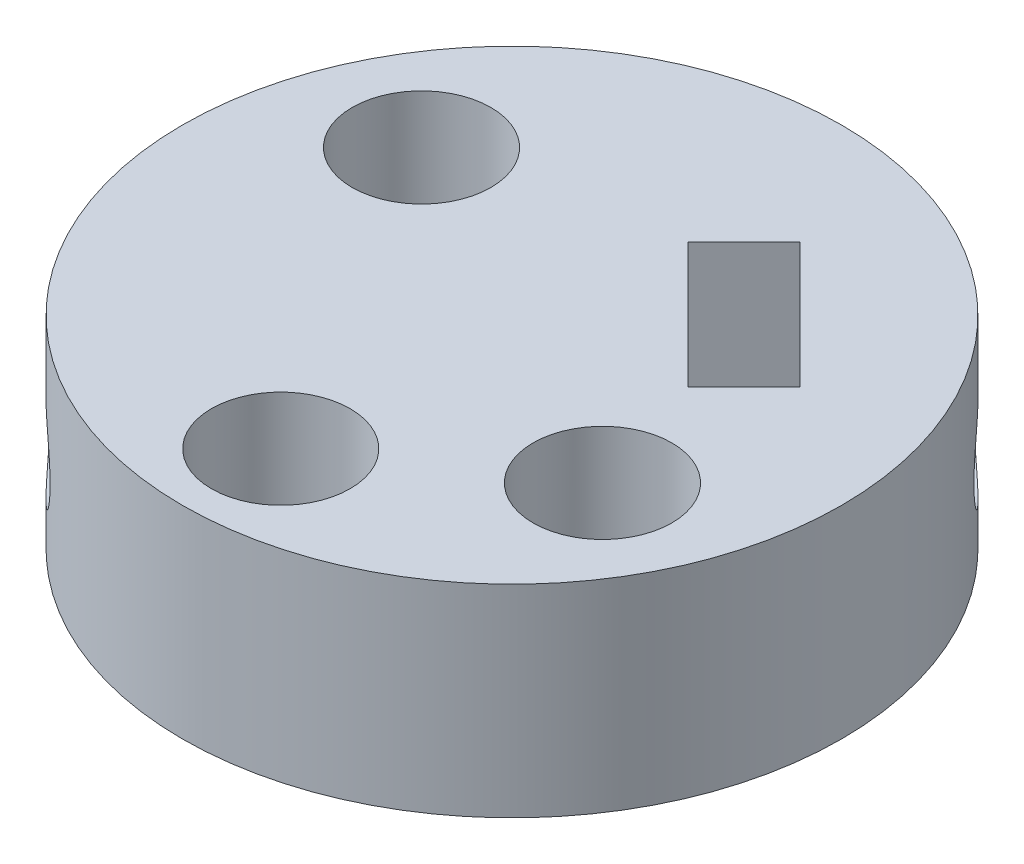
SolidWorks part; units mm, degrees
material "ABS"
ref_plane "Plano frontal" through (0, 0, 0) normal (0, 0, 1) x (1, 0, 0)
ref_plane "Plano superior" through (0, 0, 0) normal (0, 1, 0) x (1, 0, 0)
ref_plane "Plano direito" through (0, 0, 0) normal (1, 0, 0) x (0, 0, -1)
sketch "Esboço1" plane through (0, 0, 0) normal (0, 1, 0) x (1, 0, 0)
  circle A4 centre (-6.59, 3.46) radius 2.4
  circle A6 centre (6.59, -3.46) radius 2.4
  circle A8 centre (0, -8) radius 2.4
sketch "Esboço2" plane through (0, 0, 0) normal (0, 1, 0) x (1, 0, 0)
  circle A0 centre (0, 0) radius 11.4
extrude "Ressalto-extrusão3" add sketch "Esboço2" along normal blind 7
extrude "Corte-extrusão4" cut sketch "Esboço1" along normal blind 15 contours A6 | A4 | A8
sketch "Esboço3" plane through (0, 7, 0) normal (0, 1, 0) x (1, 0, 0)
  line L2 (0.8, 0.8) -> (0.8, 2.2627)
  line L3 (-0.8, 0.8) -> (-0.8, 2.2627)
  line L4 (-0.8, 2.2627) -> (-0.8, 0.8)
  line L5 (0.8, -0.8) -> (0.8, -2.2627)
  line L8 (0.8, 0.8) -> (2.2627, 0.8)
  line L9 (2.2627, 0.8) -> (0.8, 0.8)
  line L10 (0.8, -0.8) -> (2.2627, -0.8)
  line L11 (2.2627, -0.8) -> (0.8, -0.8)
  line L12 (-0.8, -0.8) -> (-2.2627, -0.8)
  line L13 (-0.8, 0.8) -> (-2.2627, 0.8)
  line L14 (-0.8, -0.8) -> (-0.8, -2.2627)
  arc A0 (0.8, 2.2627) -> (-0.8, 2.2627) centre (0, 0) ccw
  arc A1 (-2.2627, 0.8) -> (-2.2627, -0.8) centre (0, 0) ccw
  arc A2 (-0.8, -2.2627) -> (0.8, -2.2627) centre (0, 0) ccw
  arc A3 (2.2627, -0.8) -> (2.2627, 0.8) centre (0, 0) ccw
extrude "Ressalto-extrusão4" [suppressed] add sketch "Esboço3" along normal blind 9 contours L10 A3 L8 L2 A0 L3 L13 A1 L12 L14 A2 L5
sketch "Esboço4" plane through (0, 0, 0) normal (0, -1, 0) x (-1, 0, 0)
  circle A1 centre (0, 0) radius 2
sketch "Esboço6" plane through (0, 0, 0) normal (0, -1, 0) x (1, 0, 0)
  circle A0 centre (0, 0) radius 4.3
extrude "Ressalto-extrusão5" add sketch "Esboço6" along normal blind 2
extrude "Corte-extrusão7" cut sketch "Esboço4" against normal blind 5.05 and the other way blind 4
sketch "Esboço7" plane through (0, 0, 0) normal (0, -1, 0) x (1, 0, 0)
  line L0 (0, 0) -> (3.0406, -3.0406) construction
  line L1 (3.0406, -3.0406) -> (5.1972, -0.8839)
  line L2 (3.0406, -3.0406) -> (0.8485, -5.2326)
  line L3 (0.8485, -5.2326) -> (2.7931, -7.1771)
  line L4 (5.1972, -0.8839) -> (7.1418, -2.8284)
  line L5 (7.1418, -2.8284) -> (2.7931, -7.1771)
extrude "Corte-extrusão8" cut sketch "Esboço7" against normal blind 10.5 contours L5 L4 L1 L2 L3 region at (3.9952, 0, -4.0305)
sketch "Esboço8" plane through (3.0406, 0, -3.0406) normal (0.7071, 0, -0.7071) x (-0.7071, 0, -0.7071)
  line L0 (3.1, 0) -> (0, 0) construction
  circle A0 centre (0, 3) radius 1.5
  dimension "D1" = 3
extrude "Corte-extrusão9" cut sketch "Esboço8" against normal blind 20 and the other way blind 9
fillet "Filete1" radius 0.9 2 edges at (0, -2, -4.3) (0, 0, 4.3) tangent propagation no
sketch "Esboço9" plane through (0, 0, 0) normal (0, -1, 0) x (1, 0, 0)
  circle A0 centre (6.59, 3.46) radius 2.8
  circle A1 centre (0, 8) radius 2.8
  circle A3 centre (-6.59, -3.46) radius 2.8
extrude "Corte-extrusão10" cut sketch "Esboço9" against normal blind 1.65
